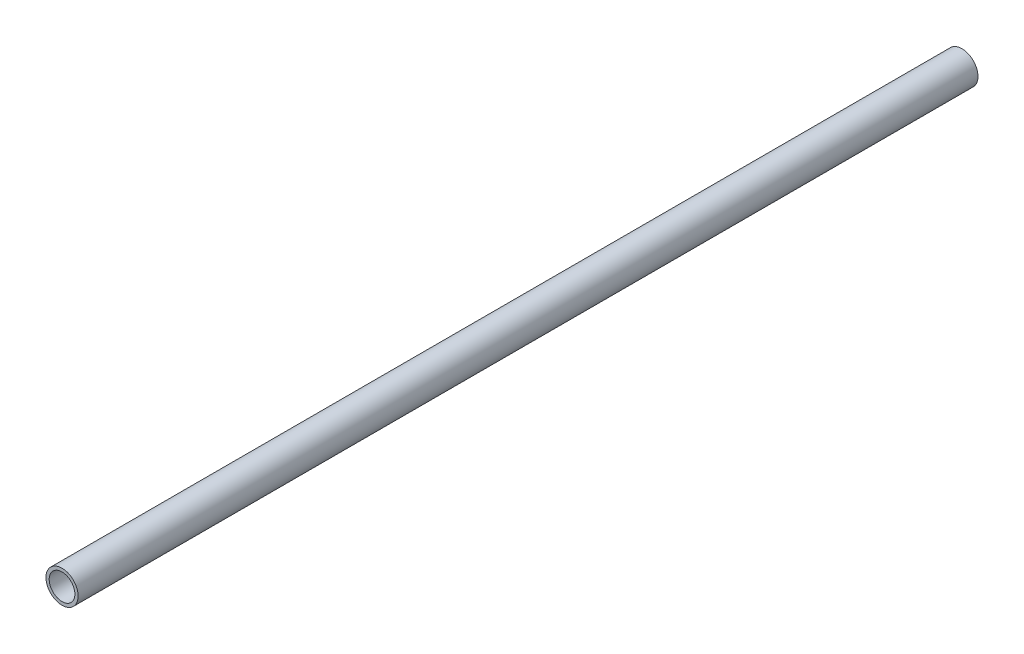
SolidWorks part; units mm, degrees
material "6061 Alloy"
ref_plane "Front Plane" through (0, 0, 0) normal (0, 0, 1) x (1, 0, 0)
ref_plane "Top Plane" through (0, 0, 0) normal (0, 1, 0) x (1, 0, 0)
ref_plane "Right Plane" through (0, 0, 0) normal (1, 0, 0) x (0, 0, -1)
sketch "Sketch1" plane through (0, 0, 0) normal (0, 0, 1) x (1, 0, 0)
  circle A0 centre (390.7614, 31.0815) radius 7.5
  circle A1 centre (390.7614, 31.0815) radius 6
extrude "Boss-Extrude1" add sketch "Sketch1" along normal blind 420
